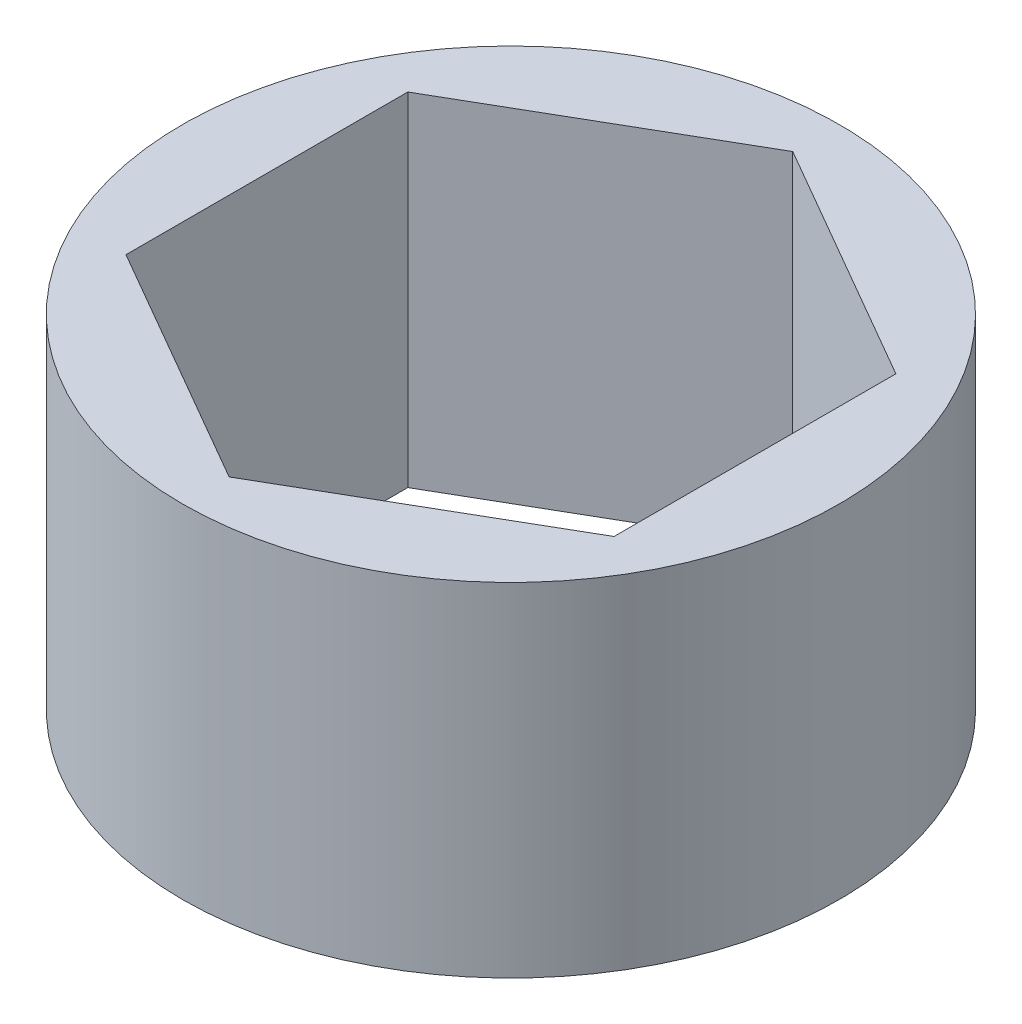
SolidWorks part; units mm, degrees
material "PET"
ref_plane "Front Plane" through (0, 0, 0) normal (0, 0, 1) x (1, 0, 0)
ref_plane "Top Plane" through (0, 0, 0) normal (0, 1, 0) x (1, 0, 0)
ref_plane "Right Plane" through (0, 0, 0) normal (1, 0, 0) x (0, 0, -1)
sketch "Sketch1" plane through (0, 0, 0) normal (0, 1, 0) x (1, 0, 0)
  line L1 (0, 7.6256) -> (-6.604, 3.8128)
  line L2 (-6.604, 3.8128) -> (-6.604, -3.8128)
  line L3 (-6.604, -3.8128) -> (0, -7.6256)
  line L4 (0, -7.6256) -> (6.604, -3.8128)
  line L5 (6.604, -3.8128) -> (6.604, 3.8128)
  line L6 (6.604, 3.8128) -> (0, 7.6256)
  circle A0 centre (0, 0) radius 8.89
  circle A2 centre (0, 0) radius 6.604 construction
  dimension "D1" = 13.208
  dimension "D2" = 17.78
extrude "Boss-Extrude1" add sketch "Sketch1" along normal mid plane 9.271
